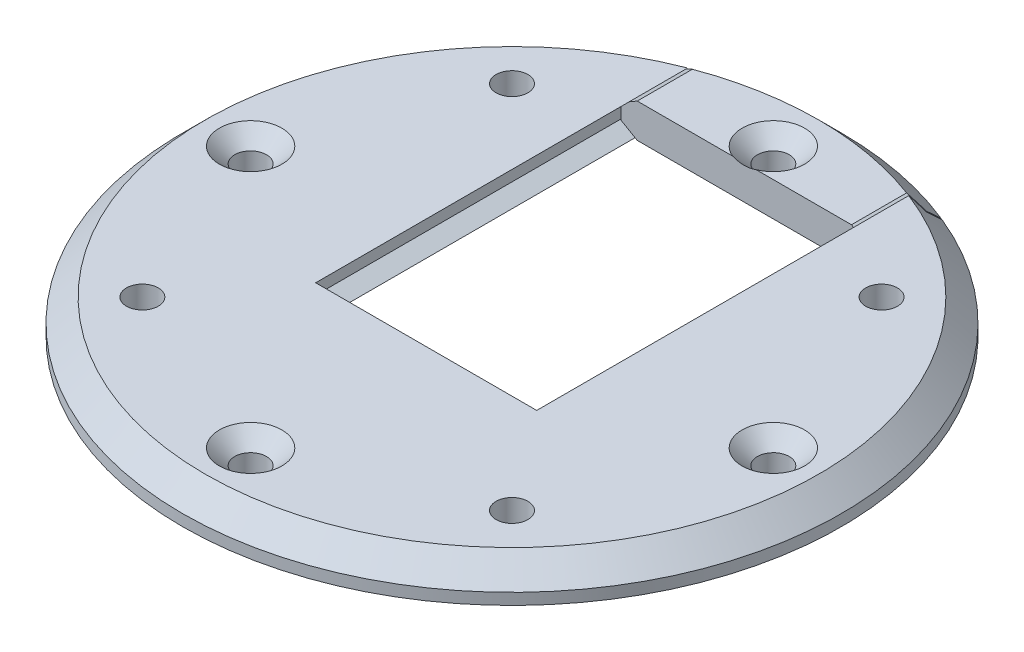
SolidWorks part; units mm, degrees
ref_plane "Front Plane" through (0, 0, 0) normal (0, 0, 1) x (1, 0, 0)
ref_plane "Top Plane" through (0, 0, 0) normal (0, 1, 0) x (1, 0, 0)
ref_plane "Right Plane" through (0, 0, 0) normal (1, 0, 0) x (0, 0, -1)
sketch "Sketch1" plane through (0, 0, 0) normal (0, 1, 0) x (1, 0, 0)
  circle A0 centre (0, 0) radius 29
  dimension "D1" = 58
extrude "Boss-Extrude1" add sketch "Sketch1" along normal mid plane 3
sketch "Sketch2" plane through (0, 1.5, 0) normal (0, 1, 0) x (1, 0, 0)
  line L0 (-11.025, 7.55) -> (-11.025, 29)
  line L1 (-11.025, -7.55) -> (11.025, -7.55)
  line L2 (-11.025, -7.55) -> (-11.025, 7.55)
  line L3 (-11.025, 7.55) -> (11.025, 7.55) construction
  line L4 (11.025, -7.55) -> (11.025, 7.55)
  line L5 (-11.025, -7.55) -> (11.025, 7.55) construction
  line L6 (-11.025, 7.55) -> (11.025, -7.55) construction
  line L7 (-11.025, 29) -> (11.025, 29)
  line L8 (11.025, 29) -> (11.025, 7.55)
  circle A0 centre (0, 0) radius 29 construction
  point P0 (0, 0)
  dimension "D1" = 7.55
  dimension "D2" = 22.05
extrude "Cut-Extrude1" cut sketch "Sketch2" against normal through all
sketch "Sketch3" plane through (0, 0, 7.55) normal (0, 0, -1) x (-1, 0, 0)
  line L0 (0, -1.5) -> (0, 1.5) construction
  line L1 (11.025, -1.5) -> (-11.025, -1.5) construction
  line L2 (11.025, 1.5) -> (-11.025, 1.5) construction
  line L3 (-11.525, -1.5) -> (-9.726, -1.5)
  line L5 (-9.726, -1.5) -> (-11.025, -0.75)
  line L6 (-11.025, -1.5) -> (-11.025, 1.5) construction
  line L7 (-11.025, -0.75) -> (-11.025, 0.75)
  line L8 (-11.025, 0.75) -> (-9.726, 1.5)
  line L9 (-9.726, 1.5) -> (-11.525, 1.5)
  line L10 (29, 1.5) -> (-29, 1.5) construction
  line L11 (-11.525, 1.5) -> (-11.525, -1.5)
  line L12 (-29, -1.5) -> (29, -1.5) construction
  line L13 (-11.025, -1.5) -> (-11.025, 1.5) construction
  line L21 (11.525, 1.5) -> (11.525, -1.5)
  line L22 (9.726, 1.5) -> (11.525, 1.5)
  line L23 (11.025, 0.75) -> (9.726, 1.5)
  line L24 (11.025, -0.75) -> (11.025, 0.75)
  line L25 (9.726, -1.5) -> (11.025, -0.75)
  line L26 (11.525, -1.5) -> (9.726, -1.5)
  point P10 (-11.025, 0)
  dimension "D1" = 0.5
  dimension "D2" = 60
  dimension "D3" = 1.5
extrude "Boss-Extrude2" add sketch "Sketch3" along normal up to surface (34.1615 mm away) up to face at (0, 0, 1.0887)
ref_plane "Plane1" through (0, 0, -20.45) normal (0, 0, -1) x (-1, 0, 0)
sketch "Sketch6" plane through (0, 0, -20.45) normal (0, 0, -1) x (-1, 0, 0)
  line L0 (-9.726, -1.5) -> (-11.025, -0.75) construction
  line L1 (-11.025, -0.75) -> (-11.025, 0.75) construction
  line L2 (-11.025, 0.75) -> (-9.726, 1.5) construction
  line L3 (-9.726, -1.5) -> (-11.025, -0.75) construction
  line L4 (-11.025, -0.75) -> (-11.025, 0.75) construction
  line L5 (-11.025, 0.75) -> (-9.726, 1.5) construction
  line L6 (-9.426, 1.5) -> (-10.875, 0.6634)
  line L7 (9.726, 1.5) -> (-9.726, 1.5) construction
  line L8 (-10.875, 0.6634) -> (-10.875, -0.6634)
  line L9 (-10.875, -0.6634) -> (-9.426, -1.5)
  line L10 (9.726, -1.5) -> (-9.726, -1.5) construction
  line L11 (0, 0) -> (0, 1.5) construction
  line L12 (10.875, -0.6634) -> (9.426, -1.5)
  line L13 (10.875, 0.6634) -> (10.875, -0.6634)
  line L14 (9.426, 1.5) -> (10.875, 0.6634)
  line L15 (-10.875, 0.6634) -> (-10.95, 0.7933) construction
  line L16 (-10.875, 0.6634) -> (-11.025, 0.6634) construction
  line L17 (10.875, -0.6634) -> (9.426, -1.5)
  line L18 (10.875, 0.6634) -> (10.875, -0.6634)
  line L19 (9.426, 1.5) -> (10.875, 0.6634)
  line L20 (-9.426, 1.5) -> (9.426, 1.5)
  line L21 (9.426, -1.5) -> (-9.426, -1.5)
  dimension "D1" = 0.15
extrude "Boss-Extrude3" add sketch "Sketch6" along normal up to surface (6.4337 mm away) separate body contours L21 L12 L13 L14 L20 L6 L8 L9 region at (0, 0, -20.45) up to face at (0, 0, -12.9953)
chamfer "Chamfer1" distance 2 angle 45 1 edges at (0, 1.5, 29)
chamfer "Chamfer2" distance 2 angle 45 2 edges at (-4.7783, 1.5, -28.6036) (4.7783, 1.5, -28.6036)
sketch "Sketch5" plane through (0, 1.5, 0) normal (0, 1, 0) x (1, 0, 0)
  circle A0 centre (0, 0) radius 23 construction
  circle A1 centre (0, 23) radius 1.4
  circle A2 centre (16.2635, 16.2635) radius 1.4
  circle A3 centre (23, 0) radius 1.4
  circle A4 centre (16.2635, -16.2635) radius 1.4
  circle A5 centre (0, -23) radius 1.4
  circle A6 centre (-16.2635, -16.2635) radius 1.4
  circle A7 centre (-23, 0) radius 1.4
  circle A8 centre (-16.2635, 16.2635) radius 1.4
  point P21 (0, 0)
  dimension "D1" = 46
  dimension "D2" = 2.8
  dimension "D3" = 8
extrude "Cut-Extrude2" cut sketch "Sketch5" against normal through all
hole_wizard "CSK for M2.5 Flat Head Machine Screw1" positions "Sketch7" profile "Sketch8" countersink size "M2.5" standard "ANSI Metric" end condition through all
sketch "Sketch7" plane through (0, 1.5, 0) normal (0, 1, 0) x (1, 0, 0)
  circle A0 centre (0, 23) radius 1.125 construction
  point P13 (0, 23)
  point P16 (23, 0)
  point P19 (0, -23)
  point P22 (-23, 0)
sketch "Sketch8" plane through (0, 1.5, -23) normal (1, 0, 0) x (0, 0, 1)
  line L0 (0, 0) -> (0, 3)
  line L1 (0, 3) -> (1.35, 3)
  line L2 (1.35, 3) -> (1.35, 1.4)
  line L3 (1.35, 1.4) -> (2.75, 0)
  line L5 (2.75, 0) -> (0, 0)
  line L6 (-1.35, 1.4) -> (-2.75, 0) construction
  line L11 (0, -6.35) -> (0, 107.95) construction
  dimension "Thru Hole Dia." = 2.7
  dimension "Thru Hole Depth" = 3
  dimension "Near C'Sink Dia." = 5.5
  dimension "Near C'Sink Angle" = 90
sketch "Sketch10" [suppressed] plane through (0, 1.5, 0) normal (0, 1, 0) x (1, 0, 0)
  line L0 (0, 0) -> (0, -30) construction
  line L1 (15, -12.5) -> (11.5, -12.5) construction
  line L6 (-15, 12.5) -> (-11.5, 12.5) construction
  line L7 (-15, 12.5) -> (-15, -12.5) construction
  line L8 (-15, -12.5) -> (-11.5, -12.5) construction
  line L9 (-11.5, 12.5) -> (-11.5, -12.5) construction
  line L10 (-11.5, -12.5) -> (11.5, -12.5) construction
  line L11 (-11.5, -12.5) -> (-11.5, -9) construction
  line L12 (-11.5, -9) -> (11.5, -9) construction
  line L13 (11.5, -12.5) -> (11.5, -9) construction
  line L14 (11.5, 12.5) -> (11.5, -12.5) construction
  line L15 (15, 12.5) -> (11.5, 12.5) construction
  line L16 (15, 12.5) -> (15, -12.5) construction
  line L17 (0, 0) -> (-11.5, 0) construction
  line L18 (-11.5, -9) -> (-11.5, 12.5)
  line L19 (-11.5, 12.5) -> (-15, 12.5)
  line L20 (-15, 12.5) -> (-15, -12.5)
  line L21 (-15, -12.5) -> (15, -12.5)
  line L22 (15, -12.5) -> (15, 12.5)
  line L23 (15, 12.5) -> (11.5, 12.5)
  line L24 (11.5, 12.5) -> (11.5, -9)
  line L25 (11.5, -9) -> (-11.5, -9)
  arc A0 (-11.025, 27.9007) -> (11.025, 27.9007) centre (0, 0) ccw construction
  point P18 (-11.5, 0)
  point P36 (0, -12.5)
  point P37 (0, -9)
  dimension "D5" = 30
  dimension "D1" = 3.5
  dimension "D2" = 3.5
  dimension "D3" = 23
  dimension "D4" = 25
  dimension "D6" = 25
extrude "Boss-Extrude4" [suppressed] add sketch "Sketch10" along normal blind 5
sketch "Sketch11" [suppressed] plane through (0, 0, 9) normal (0, 0, -1) x (-1, 0, 0)
  line L0 (-11.5, 6.5) -> (11.5, 6.5) construction
  line L1 (0, 6.5) -> (-2.45, 5.0855) construction
  line L2 (-2.45, 5.0855) -> (-2.45, 2.2565)
  line L3 (-2.45, 2.2565) -> (0, 0.842)
  line L4 (0, 0.842) -> (2.45, 2.2565)
  line L5 (2.45, 2.2565) -> (2.45, 5.0855)
  line L6 (2.45, 5.0855) -> (0, 6.5) construction
  line L7 (-2.45, 5.0855) -> (-2.45, 6.5)
  line L8 (-2.45, 6.5) -> (2.45, 6.5)
  line L9 (2.45, 6.5) -> (2.45, 5.0855)
  circle A0 centre (0, 3.671) radius 2.45 construction
  dimension "D1" = 4.9
extrude "Cut-Extrude3" [suppressed] cut sketch "Sketch11" against normal blind 2
chamfer "Chamfer3" [suppressed] distance 3.5 angle 45
sketch "Sketch12" [suppressed] plane through (-11.5, 0, 0) normal (1, 0, 0) x (0, 0, -1)
  line L0 (0, 0) -> (0, 6.5) construction
  line L1 (-9, 6.5) -> (9, 6.5) construction
  line L2 (-9, 5.0855) -> (-9, 6.5)
  line L3 (-6.55, 6.5) -> (-9, 5.0855) construction
  line L4 (-9, 5.0855) -> (-9, 2.2565)
  line L5 (-9, 2.2565) -> (-6.55, 0.842)
  line L6 (-6.55, 0.842) -> (-4.1, 2.2565)
  line L7 (-4.1, 2.2565) -> (-4.1, 5.0855)
  line L8 (-4.1, 5.0855) -> (-6.55, 6.5) construction
  line L9 (-9, 6.5) -> (-4.1, 6.5)
  line L10 (-4.1, 6.5) -> (-4.1, 5.0855)
  line L11 (9, 6.5) -> (4.1, 6.5)
  line L12 (9, 5.0855) -> (9, 6.5)
  line L13 (9, 5.0855) -> (9, 2.2565)
  line L14 (9, 2.2565) -> (6.55, 0.842)
  line L15 (6.55, 0.842) -> (4.1, 2.2565)
  line L16 (4.1, 2.2565) -> (4.1, 5.0855)
  line L17 (4.1, 6.5) -> (4.1, 5.0855)
  line L18 (-9, 6.5) -> (-9, 1.5) construction
  circle A0 centre (-6.55, 3.671) radius 2.45 construction
  dimension "D2" = 4.9
extrude "Cut-Extrude4" [suppressed] cut sketch "Sketch12" against normal blind 2
mirror "Mirror1" [suppressed] about plane through (0, 0, 0) normal (1, 0, 0)
sketch "Sketch13" [suppressed] plane through (0, 0, 11) normal (0, 0, -1) x (-1, 0, 0)
  circle A0 centre (0, 3.671) radius 1.4
  dimension "D1" = 2.8
extrude "Cut-Extrude5" [suppressed] cut sketch "Sketch13" against normal blind 2
sketch "Sketch14" [suppressed] plane through (-15, 0, 0) normal (-1, 0, 0) x (0, 0, 1)
  line L0 (0, 6.5) -> (0, 0) construction
  line L1 (-9, 6.5) -> (9, 6.5) construction
  circle A0 centre (6.55, 3.671) radius 1.4
  circle A1 centre (-6.55, 3.671) radius 1.4
  dimension "D1" = 2.8
extrude "Cut-Extrude6" [suppressed] cut sketch "Sketch14" against normal through all both and the other way through all
sketch "Sketch15" plane through (0, 0, 0) normal (0, 1, 0) x (1, 0, 0)
  line L0 (0, 0) -> (-20.5061, 20.5061) construction
  line L1 (0, 0) -> (0, -29) construction
  arc A0 (-11.025, 26.8226) -> (11.025, 26.8226) centre (0, 0) ccw construction
  circle A1 centre (-21.2132, 21.2132) radius 1.5
  circle A2 centre (21.2132, 21.2132) radius 1.5
  circle A3 centre (21.2132, -21.2132) radius 1.5
  circle A4 centre (-21.2132, -21.2132) radius 1.5
  point P17 (0, 0)
  dimension "D2" = 3
  dimension "D1" = 135
  dimension "D3" = 1
  dimension "D4" = 4
extrude "Cut-Extrude7" [suppressed] cut sketch "Sketch15" against normal through all
equation "\"m2.5 width\"= 4.9mm"
equation "\"D1@Sketch11\"=\"m2.5 width\""
equation "\"D2@Sketch12\"=\"m2.5 width\""
